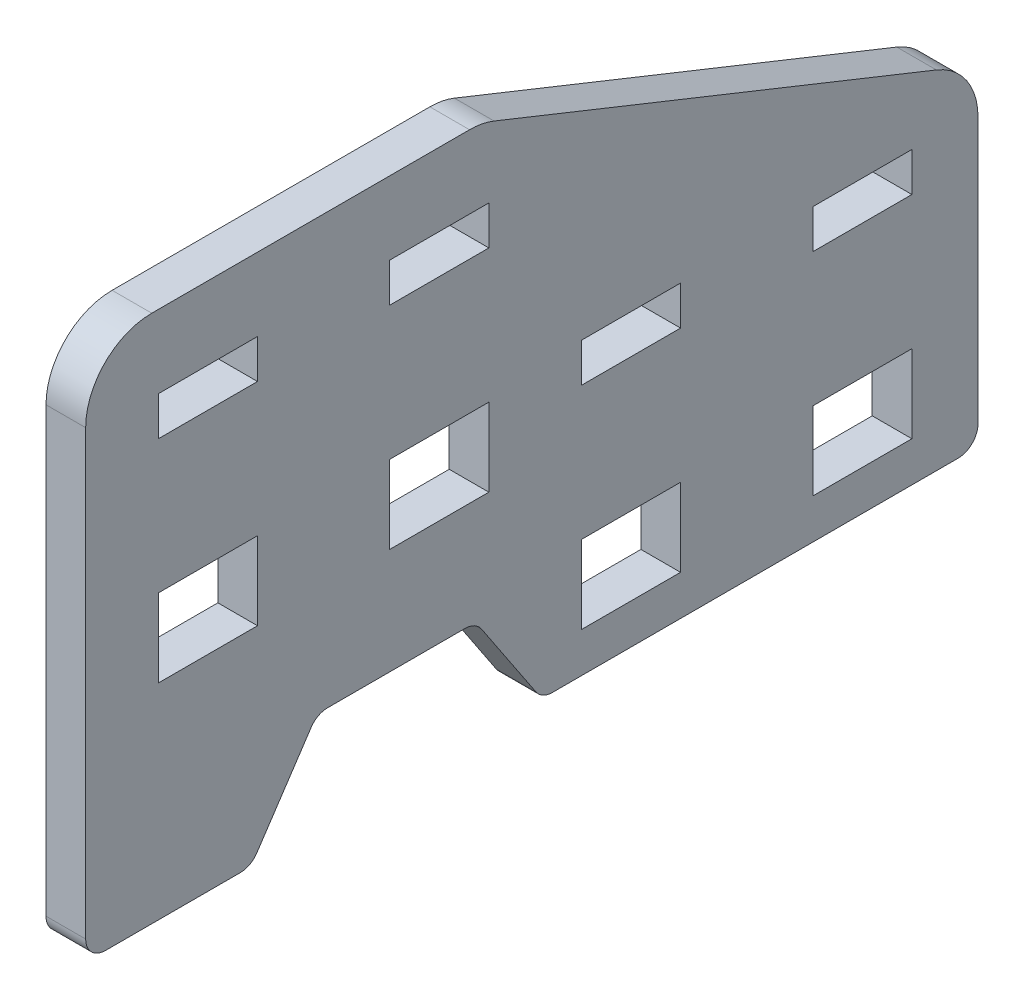
SolidWorks part; units mm, degrees
ref_plane "Front" through (0, 0, 0) normal (0, 0, 1) x (1, 0, 0)
ref_plane "Top" through (0, 0, 0) normal (0, 1, 0) x (1, 0, 0)
ref_plane "Right" through (0, 0, 0) normal (1, 0, 0) x (0, 0, -1)
sketch "Skizze1" plane through (0, 0, 0) normal (1, 0, 0) x (0, 0, -1)
  line L0 (0, 0) -> (25, 0)
  line L1 (25, 0) -> (35, 15)
  line L2 (35, 15) -> (59, 15)
  line L3 (59, 15) -> (69, 0)
  line L4 (69, 0) -> (135, 0)
  line L5 (135, 0) -> (135, 50)
  line L6 (135, 50) -> (60, 80)
  line L7 (60, 80) -> (0, 80)
  line L8 (0, 80) -> (0, 0)
  line L9 (35, 15) -> (25, 15) construction
  line L10 (25, 15) -> (25, 0) construction
  line L11 (59, 15) -> (69, 15) construction
  line L12 (69, 15) -> (69, 0) construction
  dimension "D1" = 80
  dimension "135" = 135
  dimension "D3" = 66
  dimension "D4" = 15
  dimension "D5" = 10
  dimension "D6" = 60
  dimension "D7" = 50
  dimension "D8" = 25
extrude "Grundform" add sketch "Skizze1" along normal blind 6
sketch "Skizze2" plane through (6, 0, 0) normal (1, 0, 0) x (0, 0, -1)
  line L0 (90, 41) -> (110, 41) construction
  line L1 (75, 43.95) -> (90, 43.95)
  line L2 (75, 43.95) -> (75, 38.05)
  line L3 (75, 38.05) -> (90, 38.05)
  line L4 (90, 43.95) -> (90, 38.05)
  line L5 (100, 41) -> (100, 9) construction
  line L6 (100, 25) -> (141.5957, 25) construction
  line L7 (110, 43.95) -> (110, 38.05)
  line L8 (125, 38.05) -> (110, 38.05)
  line L9 (125, 43.95) -> (125, 38.05)
  line L10 (125, 43.95) -> (110, 43.95)
  line L11 (90, 9) -> (110, 9) construction
  line L12 (125, 6.05) -> (110, 6.05)
  line L13 (125, 6.05) -> (125, 11.95)
  line L14 (125, 11.95) -> (110, 11.95)
  line L15 (110, 6.05) -> (110, 11.95)
  line L16 (90, 6.05) -> (90, 11.95)
  line L17 (75, 11.95) -> (90, 11.95)
  line L18 (75, 6.05) -> (75, 11.95)
  line L19 (75, 6.05) -> (90, 6.05)
  line L20 (135, 0) -> (135, 50) construction
  line L21 (69, 0) -> (135, 0) construction
  line L22 (46, 66) -> (36, 66) construction
  line L39 (61, 68.95) -> (61, 63.05)
  line L56 (46, 68.95) -> (46, 63.05)
  line L57 (36, 66) -> (36, 34) construction
  line L58 (36, 50) -> (90.9252, 50) construction
  line L62 (26, 68.95) -> (26, 63.05)
  line L69 (11, 68.95) -> (11, 63.05)
  line L71 (11, 63.05) -> (26, 63.05)
  line L72 (11, 68.95) -> (26, 68.95)
  line L73 (61, 68.95) -> (46, 68.95)
  line L74 (61, 63.05) -> (46, 63.05)
  line L75 (46, 34) -> (36, 34) construction
  line L76 (36, 66) -> (26, 66) construction
  line L80 (11, 31.05) -> (26, 31.05)
  line L81 (11, 31.05) -> (11, 36.95)
  line L82 (11, 36.95) -> (26, 36.95)
  line L83 (26, 31.05) -> (26, 36.95)
  line L84 (46, 31.05) -> (46, 36.95)
  line L85 (61, 36.95) -> (46, 36.95)
  line L86 (61, 31.05) -> (61, 36.95)
  line L87 (61, 31.05) -> (46, 31.05)
  dimension "D1" = 5.9
  dimension "D2" = 15
  dimension "D3" = 20
  dimension "D4" = 32
  dimension "D5" = 35
  dimension "D6" = 25
  dimension "D7" = 64
  dimension "D8" = 25
  dimension "D9" = 20
extrude "Zapfendurchbruch" cut sketch "Skizze2" against normal through all
fillet "Verrundung1" radius 10 3 edges at (3, 80, 0) (3, 80, -60) (3, 50, -135)
fillet "Verrundung2" radius 3 6 edges at (3, 0, 0) (3, 0, -25) (3, 15, -35) (3, 15, -59) (3, 0, -69) (3, 0, -135)
sketch "Skizze3" plane through (0, 0, 0) normal (-1, 0, 0) x (0, 0, 1)
  line L0 (-125, 11.95) -> (-110, 11.95) construction
  line L1 (-125, 11.95) -> (-110, 11.95)
  line L2 (-125, 11.95) -> (-125, 17.85)
  line L3 (-125, 17.85) -> (-110, 17.85)
  line L4 (-110, 11.95) -> (-110, 17.85)
  line L5 (-90, 11.95) -> (-75, 11.95)
  line L6 (-90, 11.95) -> (-90, 17.85)
  line L7 (-90, 17.85) -> (-75, 17.85)
  line L8 (-75, 11.95) -> (-75, 17.85)
  line L9 (-61, 36.95) -> (-46, 36.95)
  line L10 (-61, 36.95) -> (-61, 42.85)
  line L11 (-61, 42.85) -> (-46, 42.85)
  line L12 (-46, 36.95) -> (-46, 42.85)
  line L13 (-26, 36.95) -> (-11, 36.95)
  line L14 (-26, 36.95) -> (-26, 42.85)
  line L15 (-26, 42.85) -> (-11, 42.85)
  line L16 (-11, 36.95) -> (-11, 42.85)
  line L17 (-125, 6.05) -> (-125, 11.95) construction
  point P24 (0, 0)
  point P27 (-11, 36.7598)
extrude "Zapfendurchbruch 2" cut sketch "Skizze3" against normal through all
